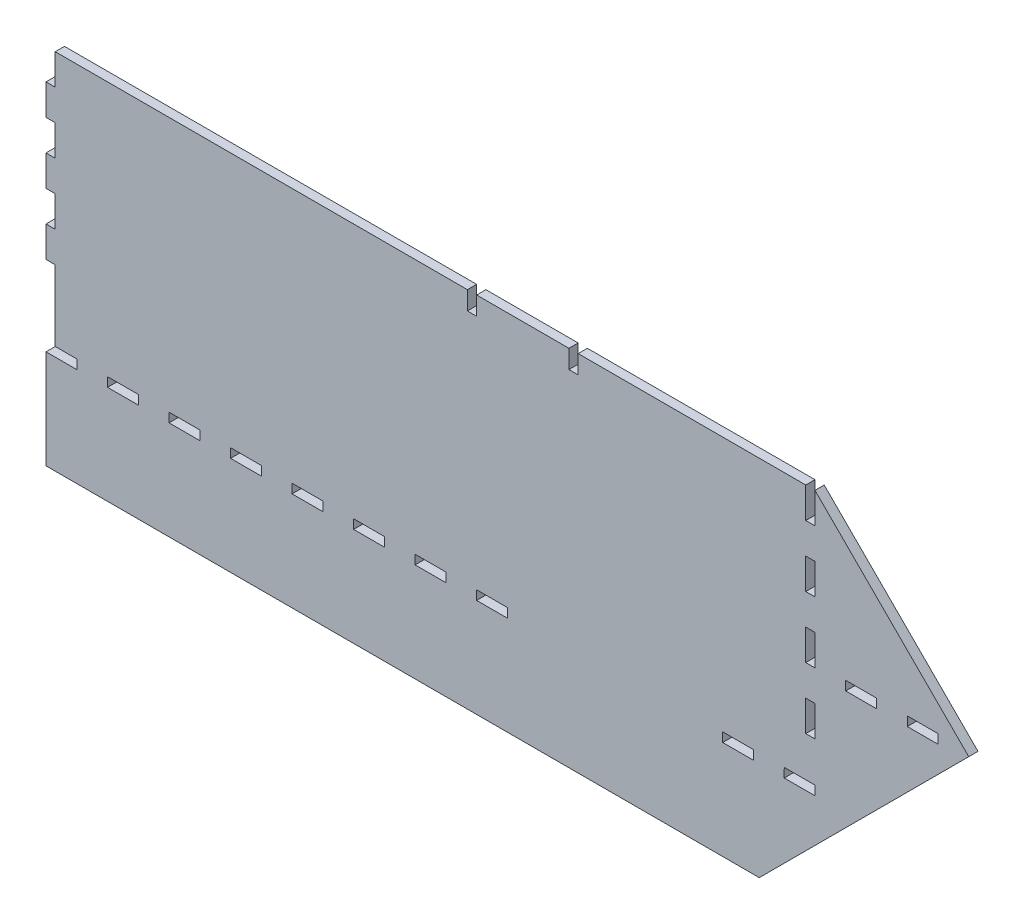
SolidWorks part; units mm, degrees
ref_plane "Front Plane" through (0, 0, 0) normal (0, 0, 1) x (1, 0, 0)
ref_plane "Top Plane" through (0, 0, 0) normal (0, 1, 0) x (1, 0, 0)
ref_plane "Right Plane" through (0, 0, 0) normal (1, 0, 0) x (0, 0, -1)
sketch "Sketch1" plane through (0, 0, 0) normal (0, 0, 1) x (1, 0, 0)
  line L0 (-112.631, -63.8403) -> (-112.631, -53.7284)
  line L1 (134.369, 32.2716) -> (60.379, 32.2716)
  line L2 (-72.631, -50.7284) -> (-62.631, -50.7284)
  line L3 (-62.631, 32.2716) -> (24.379, 32.2716)
  line L4 (137.369, 32.2716) -> (187.369, -17.7284)
  line L5 (187.369, -17.7284) -> (137.369, -67.7284)
  line L7 (42.379, 32.2716) -> (27.379, 32.2716)
  line L8 (27.379, 32.2716) -> (27.379, 26.2716)
  line L9 (137.369, 32.2716) -> (137.369, -67.7284) construction
  line L10 (137.369, -17.7284) -> (187.369, -17.7284) construction
  line L11 (157.369, -16.2284) -> (147.369, -16.2284)
  line L12 (177.369, -16.2284) -> (167.369, -16.2284)
  line L13 (177.369, -16.2284) -> (177.369, -19.2284)
  line L14 (177.369, -19.2284) -> (167.369, -19.2284)
  line L15 (167.369, -16.2284) -> (167.369, -19.2284)
  line L16 (177.369, -16.2284) -> (167.369, -19.2284) construction
  line L17 (177.369, -19.2284) -> (167.369, -16.2284) construction
  line L18 (157.369, -16.2284) -> (157.369, -19.2284)
  line L19 (157.369, -19.2284) -> (147.369, -19.2284)
  line L20 (147.369, -16.2284) -> (147.369, -19.2284)
  line L21 (137.3812, -50.7284) -> (127.3812, -50.7284)
  line L22 (137.3812, -50.7284) -> (137.3692, -53.7284)
  line L23 (137.3692, -53.7284) -> (127.3692, -53.7284)
  line L24 (127.3812, -50.7284) -> (127.3692, -53.7284)
  line L25 (137.3812, -50.7284) -> (127.3692, -53.7284) construction
  line L26 (137.3692, -53.7284) -> (127.3812, -50.7284) construction
  line L27 (117.3811, -50.7284) -> (107.3787, -50.7284)
  line L28 (117.3811, -50.7284) -> (117.3691, -53.7284)
  line L29 (117.3691, -53.7284) -> (107.3691, -53.7284)
  line L30 (107.3787, -50.7284) -> (107.3691, -53.7284)
  line L31 (117.3811, -50.7284) -> (107.3691, -53.7284) construction
  line L32 (117.3691, -53.7284) -> (107.3787, -50.7284) construction
  line L33 (27.379, 26.2716) -> (24.379, 26.2716)
  line L34 (24.379, 26.2716) -> (24.379, 32.2716)
  line L35 (27.379, 32.2716) -> (57.379, 32.2716)
  line L36 (137.369, -67.7284) -> (119.2571, -85.8403)
  line L37 (60.379, 26.2716) -> (60.379, 32.2716)
  line L38 (57.379, 26.2716) -> (60.379, 26.2716)
  line L39 (57.379, 32.2716) -> (57.379, 26.2716)
  line L40 (57.379, 32.2716) -> (42.379, 32.2716)
  line L41 (60.379, 32.2716) -> (134.369, 32.2716)
  line L42 (119.2571, -85.8403) -> (-112.631, -85.8403)
  line L43 (-112.631, -85.8403) -> (-112.631, -63.8403)
  line L51 (37.3714, -50.7284) -> (27.369, -50.7284)
  line L52 (37.3714, -50.7284) -> (37.369, -53.7284)
  line L53 (37.369, -53.7284) -> (27.369, -53.7284)
  line L54 (27.369, -50.7284) -> (27.369, -53.7284)
  line L55 (37.3714, -50.7284) -> (27.369, -53.7284) construction
  line L56 (37.369, -53.7284) -> (27.369, -50.7284) construction
  line L57 (17.369, -50.7284) -> (7.369, -50.7284)
  line L58 (17.369, -50.7284) -> (17.369, -53.7284)
  line L59 (17.369, -53.7284) -> (7.369, -53.7284)
  line L60 (7.369, -50.7284) -> (7.369, -53.7284)
  line L61 (17.369, -50.7284) -> (7.369, -53.7284) construction
  line L62 (17.369, -53.7284) -> (7.369, -50.7284) construction
  line L63 (-2.631, -50.7284) -> (-12.631, -50.7284)
  line L64 (-2.631, -50.7284) -> (-2.631, -53.7284)
  line L65 (-2.631, -53.7284) -> (-12.631, -53.7284)
  line L66 (-12.631, -50.7284) -> (-12.631, -53.7284)
  line L67 (-2.631, -50.7284) -> (-12.631, -53.7284) construction
  line L68 (-2.631, -53.7284) -> (-12.631, -50.7284) construction
  line L69 (-22.631, -50.7284) -> (-32.631, -50.7284)
  line L70 (-22.631, -50.7284) -> (-22.631, -53.7284)
  line L71 (-22.631, -53.7284) -> (-32.631, -53.7284)
  line L72 (-32.631, -50.7284) -> (-32.631, -53.7284)
  line L73 (-22.631, -50.7284) -> (-32.631, -53.7284) construction
  line L74 (-22.631, -53.7284) -> (-32.631, -50.7284) construction
  line L75 (-42.631, -50.7284) -> (-52.631, -50.7284)
  line L76 (-42.631, -50.7284) -> (-42.631, -53.7284)
  line L77 (-42.631, -53.7284) -> (-52.631, -53.7284)
  line L78 (-52.631, -50.7284) -> (-52.631, -53.7284)
  line L79 (-42.631, -50.7284) -> (-52.631, -53.7284) construction
  line L80 (-42.631, -53.7284) -> (-52.631, -50.7284) construction
  line L82 (-62.631, -50.7284) -> (-62.631, -53.7284)
  line L83 (-62.631, -53.7284) -> (-72.631, -53.7284)
  line L84 (-72.631, -50.7284) -> (-72.631, -53.7284)
  line L85 (-62.631, -50.7284) -> (-72.631, -53.7284) construction
  line L86 (-62.631, -53.7284) -> (-72.631, -50.7284) construction
  line L87 (137.369, 12.2716) -> (134.369, 12.2716)
  line L88 (-82.631, -50.7284) -> (-82.631, -53.7284)
  line L89 (-82.631, -53.7284) -> (-92.631, -53.7284)
  line L90 (-92.631, -50.7284) -> (-92.631, -53.7284)
  line L91 (-82.631, -50.7284) -> (-92.631, -53.7284) construction
  line L92 (-82.631, -53.7284) -> (-92.631, -50.7284) construction
  line L94 (-102.631, -50.7284) -> (-102.631, -53.7284)
  line L95 (-102.631, -53.7284) -> (-112.631, -53.7284)
  line L97 (-102.631, -50.7284) -> (-112.631, -53.7284) construction
  line L98 (-102.631, -53.7284) -> (-107.631, -52.2284) construction
  line L99 (-62.631, -50.7284) -> (-72.631, -50.7284) [skipped]
  line L100 (-82.631, -50.7284) -> (-92.631, -50.7284) [skipped]
  line L101 (-102.631, -50.7284) -> (-112.631, -50.7284) [skipped]
  line L102 (137.369, 32.2716) -> (137.369, 22.2716)
  line L103 (137.369, 22.2716) -> (134.369, 22.2716)
  line L104 (134.369, 32.2716) -> (134.369, 22.2716)
  line L105 (137.369, 12.2716) -> (137.369, 2.2716)
  line L106 (137.369, 2.2716) -> (134.369, 2.2716)
  line L107 (134.369, 12.2716) -> (134.369, 2.2716)
  line L108 (137.369, -7.7284) -> (134.369, -7.7284)
  line L109 (137.369, -7.7284) -> (137.369, -17.7284)
  line L111 (137.369, -17.7284) -> (134.369, -17.7284)
  line L114 (157.369, -16.2284) -> (147.369, -19.2284) construction
  line L121 (134.369, -7.7284) -> (134.369, -17.7284)
  line L122 (157.369, -19.2284) -> (147.369, -16.2284) construction
  line L124 (-109.631, -50.7284) -> (-102.631, -50.7284)
  line L125 (-112.631, -52.2284) -> (-112.631, -53.3547) [skipped]
  line L126 (-62.631, 32.2716) -> (-109.631, 32.2716)
  line L127 (-112.631, -7.7284) -> (-109.631, -7.7284)
  line L128 (137.369, -27.7284) -> (134.369, -27.7284)
  line L129 (137.369, -27.7284) -> (137.369, -37.7284)
  line L130 (137.369, -37.7284) -> (134.369, -37.7284)
  line L131 (134.369, -27.7284) -> (134.369, -37.7284)
  line L132 (-112.631, 22.2716) -> (-112.631, 12.2716)
  line L133 (-109.631, -17.7284) -> (-112.631, -17.7284)
  line L134 (-112.631, -27.7284) -> (-109.631, -27.7284)
  line L135 (-109.631, -50.7284) -> (-109.631, -27.7284)
  line L136 (-109.631, 2.2716) -> (-112.631, 2.2716)
  line L137 (-112.631, 2.2716) -> (-112.631, -7.7284)
  line L138 (-109.631, 22.2716) -> (-109.631, 32.2716)
  line L139 (-109.631, 22.2716) -> (-112.631, 22.2716)
  line L140 (-112.631, 12.2716) -> (-109.631, 12.2716)
  line L141 (-109.631, -17.7284) -> (-109.631, -7.7284)
  line L142 (-112.631, -17.7284) -> (-112.631, -27.7284)
  line L143 (-109.631, 2.2716) -> (-109.631, 12.2716)
  line L144 (-92.631, -50.7284) -> (-82.631, -50.7284)
  point P5 (172.369, -17.7284)
  point P9 (151.1235, -51.5486)
  point P17 (152.369, -17.7284)
  point P19 (131.1235, -51.6165)
  point P24 (111.1235, -51.6845)
  point P44 (31.1235, -51.9564)
  point P49 (11.1235, -52.0244)
  point P54 (-8.8765, -52.0924)
  point P59 (-28.8765, -52.1604)
  point P64 (-48.8765, -52.2284)
  point P70 (-68.8765, -52.2284)
  point P75 (-88.8765, -52.2284)
  point P80 (-108.8765, -52.2284)
  dimension "D3" = 300
  dimension "D5" = 50
  dimension "D6" = 10
  dimension "D7" = 10
  dimension "D8" = 10
  dimension "D10" = 3
  dimension "D11" = 22
  dimension "D13" = 3
  dimension "D14" = 10
  dimension "D15" = 94.99
  dimension "D17" = 15
  dimension "D18" = 6
  dimension "D19" = 3
  dimension "D21" = 10
  dimension "D22" = 10
  dimension "D23" = 10
  dimension "D24" = 10
  dimension "D25" = 10
  dimension "D26" = 10
  dimension "D9" = 10
  dimension "D27" = 10
  dimension "D28" = 10
  dimension "D29" = 10
  dimension "D30" = 10
  dimension "D31" = 15
  dimension "D38" = 10
  dimension "D39" = 10
  dimension "D40" = 3
  dimension "D41" = 10
  dimension "D20" = 47
  dimension "D42" = 3
  dimension "D12" = 4
  dimension "D16" = 4
extrude "Boss-Extrude1" add sketch "Sketch1" along normal blind 3 contours L94 L95 L0 L5 L4 L3 L82 L83 L84 L88 L89 L90 L24 L21 L22 L23 L30 L27 L28 L29 region at (23.1032, -25.7803, 0)
